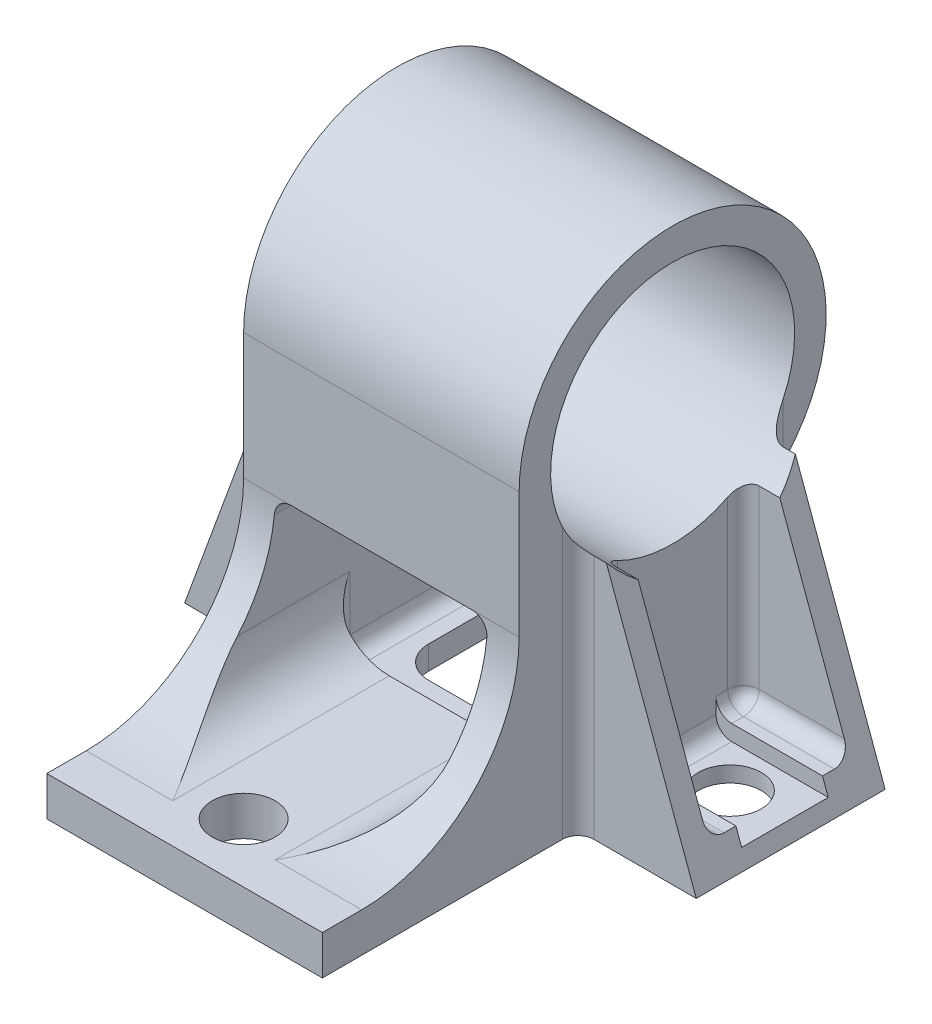
SolidWorks part; units mm, degrees
material "7075-T6 (SN)"
ref_plane "Płaszczyzna przednia" through (0, 0, 0) normal (0, 0, 1) x (1, 0, 0)
ref_plane "Płaszczyzna górna" through (0, 0, 0) normal (0, 1, 0) x (1, 0, 0)
ref_plane "Płaszczyzna prawa" through (0, 0, 0) normal (1, 0, 0) x (0, 0, -1)
sketch "Szkic1" plane through (0, 0, 0) normal (1, 0, 0) x (0, 0, -1)
  line L1 (-29.5, -41) -> (19.5, -41)
  line L2 (19.5, -41) -> (19.5, 0)
  line L4 (-44.5, -41) -> (-29.5, -41)
  line L5 (-44.5, -41) -> (-44.5, -36)
  line L6 (-44.5, -36) -> (-39.5, -36)
  line L8 (-19.5, 0) -> (-19.5, -16)
  circle A0 centre (0, 0) radius 15.5
  arc A1 (19.5, 0) -> (-19.5, 0) centre (0, 0) ccw
  arc A2 (-39.5, -36) -> (-19.5, -16) centre (-39.5, -16) ccw
  circle A3 centre (0, 0) radius 19.5 construction
  point P11 (19.5, 0)
  dimension "D1" = 31
  dimension "D5" = 20
  dimension "D3" = 41
  dimension "D4" = 25
  dimension "D6" = 5
  dimension "D2" = 4
extrude "Dodanie-wyciągnięcie2" add sketch "Szkic1" along normal mid plane 35
sketch "Szkic3" plane through (0, 0, -19.5) normal (0, 0, -1) x (-1, 0, 0)
  line L0 (-17.5, -41) -> (17.5, -41) construction
  line L1 (-13.5, -41) -> (13.5, -41)
  line L2 (-13.5, -41) -> (-13.5, -16)
  line L3 (-13.5, -16) -> (13.5, -16)
  line L4 (13.5, -41) -> (13.5, -16)
  line L5 (-17.5, -41) -> (-17.5, 0) construction
  line L6 (17.5, -41) -> (17.5, 0) construction
  line L7 (-17.5, 0) -> (17.5, 0) construction
  dimension "D1" = 4
  dimension "D2" = 4
  dimension "D3" = 16
extrude "Wytnij-wyciągnięcie2" cut sketch "Szkic3" against normal through all
sketch "Szkic5" plane through (0, -41, 0) normal (0, -1, 0) x (1, 0, 0)
  line L0 (-17.5, 44.5) -> (-17.5, -19.5) construction
  line L1 (17.5, -19.5) -> (-17.5, -19.5)
  line L2 (17.5, -19.5) -> (17.5, -4.5)
  line L3 (17.5, -4.5) -> (-17.5, -4.5)
  line L4 (-17.5, -19.5) -> (-17.5, -4.5)
  line L6 (17.5, 44.5) -> (-17.5, 44.5)
  line L7 (17.5, 44.5) -> (17.5, 29.5)
  line L8 (17.5, 29.5) -> (-17.5, 29.5)
  line L9 (-17.5, 44.5) -> (-17.5, 29.5)
  dimension "D1" = 15
  dimension "D2" = 15
extrude "Dodanie-wyciągnięcie4" add sketch "Szkic5" against normal blind 5
sketch "Szkic6" plane through (0, -36, 0) normal (0, 1, 0) x (1, 0, 0)
  line L0 (-13.5, -29.5) -> (13.5, -29.5) construction
  line L3 (-17.5, -39.5) -> (-17.5, -44.5) construction
  line L4 (13.5, 4.5) -> (-13.5, 4.5) construction
  line L5 (-17.5, -44.5) -> (-17.5, 19.5) construction
  circle A0 centre (0, -37) radius 4
  circle A1 centre (0, 12) radius 4
  dimension "D1" = 8
  dimension "D4" = 8
  dimension "D6" = 17.5
  dimension "D2" = 7.5
  dimension "D3" = 17.5
  dimension "D5" = 7.5
extrude "Wytnij-wyciągnięcie3" cut sketch "Szkic6" against normal through all
sketch "Szkic8" plane through (0, 0, 0) normal (0, 0, 1) x (1, 0, 0)
  line L0 (17.5, -41) -> (32.5, -41)
  line L1 (32.5, -41) -> (17.5, 0)
  line L2 (-17.5, -41) -> (-32.5, -41)
  line L3 (-32.5, -41) -> (-17.5, 0)
  line L4 (17.5, 0) -> (17.5, -41)
  line L5 (-17.5, 0) -> (-17.5, -41)
  dimension "D1" = 15
  dimension "D2" = 15
extrude "Dodanie-wyciągnięcie5" add sketch "Szkic8" against normal mid plane 24
sketch "Szkic9" plane through (0, 0, 0) normal (0, 1, 0) x (1, 0, 0)
  line L0 (-17.5, 12) -> (-17.5, -12) construction
  line L1 (-17.5, 9) -> (-32.5, 9)
  line L2 (-17.5, 9) -> (-17.5, -9)
  line L3 (-17.5, -9) -> (-32.5, -9)
  line L4 (-32.5, 9) -> (-32.5, -9)
  line L5 (-32.5, 12) -> (-32.5, -12) construction
  line L6 (-17.5, 12) -> (-32.5, 12) construction
  line L7 (-17.5, -12) -> (-32.5, -12) construction
  line L8 (17.5, -19.5) -> (17.5, 19.5) construction
  line L9 (17.5, 9) -> (32.5, 9)
  line L10 (17.5, 9) -> (17.5, -9)
  line L11 (17.5, -9) -> (32.5, -9)
  line L12 (32.5, 9) -> (32.5, -9)
  line L13 (32.5, 12) -> (32.5, -12) construction
  line L14 (32.5, 12) -> (17.5, 12) construction
  line L15 (32.5, -12) -> (17.5, -12) construction
  dimension "D1" = 3
  dimension "D2" = 3
  dimension "D3" = 3
  dimension "D4" = 3
extrude "Wytnij-wyciągnięcie4" cut sketch "Szkic9" along normal through all and the other way offset from surface 2 other way up to face at (0, -41, 41)
sketch "Szkic10" plane through (0, 0, 0) normal (1, 0, 0) x (0, 0, -1)
  circle A0 centre (0, 0) radius 15.5
extrude "Wytnij-wyciągnięcie5" cut sketch "Szkic10" against normal through all both and the other way through all
sketch "Szkic11" plane through (0, -39, 0) normal (0, 1, 0) x (1, 0, 0)
  line L0 (-31.7683, -9) -> (-31.7683, 9) construction
  line L1 (31.7683, 9) -> (31.7683, -9) construction
  circle A0 centre (-24.7683, 0) radius 4
  circle A1 centre (24.7683, 0) radius 4
  dimension "D1" = 8
  dimension "D3" = 8
  dimension "D2" = 7
  dimension "D4" = 7
extrude "Wytnij-wyciągnięcie6" cut sketch "Szkic11" against normal through all both and the other way through all
sketch "Szkic12" plane through (0, -41, 0) normal (0, -1, 0) x (1, 0, 0)
  line L0 (17.5, -19.5) -> (-17.5, -19.5) construction
  line L1 (-13.5, -4.5) -> (12.5, -4.5)
  line L2 (-13.5, -4.5) -> (-13.5, -19.5)
  line L3 (-13.5, -19.5) -> (12.5, -19.5)
  line L4 (12.5, -4.5) -> (12.5, -19.5)
extrude "Wytnij-wyciągnięcie7" cut sketch "Szkic12" against normal blind 5
sketch "Szkic13" plane through (0, -41, 0) normal (0, -1, 0) x (1, 0, 0)
  line L0 (-13.5, 29.5) -> (-13.5, -19.5) construction
  line L1 (-13.5, 12) -> (13.5, 12)
  line L2 (-13.5, 12) -> (-13.5, -12)
  line L3 (-13.5, -12) -> (13.5, -12)
  line L4 (13.5, 12) -> (13.5, -12)
  line L5 (13.5, 29.5) -> (13.5, -4.5) construction
extrude "Dodanie-wyciągnięcie6" add sketch "Szkic13" against normal blind 3
sketch "Szkic14" plane through (0, -41, 0) normal (0, -1, 0) x (1, 0, 0)
  line L0 (13.5, 25.2297) -> (13.5, -14.9592) construction
  line L1 (-5.5, 8) -> (5.5, 8)
  line L2 (-9.5, 4) -> (-9.5, -4)
  line L3 (-5.5, -8) -> (5.5, -8)
  line L4 (9.5, 4) -> (9.5, -4)
  line L5 (13.5, 29.5) -> (13.5, 12) construction
  line L6 (13.5, 29.5) -> (13.5, 12) construction
  line L7 (-13.5, 20.75) -> (-13.5, -14.9592) construction
  line L8 (-13.5, 29.5) -> (-13.5, 12) construction
  line L9 (-13.5, -12) -> (-13.5, -19.5) construction
  line L10 (13.5, 12) -> (-13.5, 12) construction
  line L11 (-13.5, -12) -> (12.5, -12) construction
  arc A0 (5.5, -8) -> (9.5, -4) centre (5.5, -4) ccw
  arc A1 (5.5, 8) -> (9.5, 4) centre (5.5, 4) cw
  arc A2 (-5.5, 8) -> (-9.5, 4) centre (-5.5, 4) ccw
  arc A3 (-9.5, -4) -> (-5.5, -8) centre (-5.5, -4) ccw
  dimension "D5" = 4
  dimension "D1" = 4
  dimension "D2" = 4
  dimension "D3" = 4
  dimension "D4" = 4
extrude "Wytnij-wyciągnięcie8" cut sketch "Szkic14" against normal blind 3
sketch "Szkic15" plane through (0, 0, 0) normal (1, 0, 0) x (0, 0, -1)
  line L0 (19.5, 0) -> (19.5, -41)
  line L1 (19.5, -41) -> (12, -41)
  line L2 (12, -41) -> (12, -15.3704)
  line L3 (12, -9.8107) -> (12, -41) construction
  arc A1 (12, -15.3704) -> (19.5, 0) centre (0, 0) ccw
  point P11 (19.5, 0)
extrude "Wytnij-wyciągnięcie9" cut sketch "Szkic15" against normal through all both and the other way through all contours A1 L0 L1 L2
fillet "Zaokrąglenie1" radius 10 1 edges at (0, -15.3704, -12)
fillet "Zaokrąglenie2" radius 2 4 edges at (-17.5, -25.4054, 12) (17.5, -25.4054, 12) (17.5, -14.732, -12) (-17.5, -14.732, -12)
fillet "Zaokrąglenie4" radius 2 4 edges at (13.5, -38.5, 29.5) (-13.5, -38.5, 29.5) (-13.5, -39.5, 12) (13.5, -39.5, 12)
fillet "Zaokrąglenie5" radius 2 7 edges at (17.5, -39, 0) (17.5, -25.8097, -9) (17.5, -25.8097, 9) (-17.5, -25.8097, -9) (-17.5, -39, 0) (-17.5, -25.8097, 9) (-13.5, -38, 1)
fillet "Zaokrąglenie6" radius 2 2 edges at (13.5, -16, 3.4044) (-13.5, -16, 3.4044)
sketch "Szkic16" plane through (0, 0, -12) normal (0, 0, -1) x (-1, 0, 0)
  line L1 (-13.5, -36) -> (-12.5, -36)
  line L2 (-13.5, -36) -> (-13.5, -38)
  line L3 (-13.5, -38) -> (-12.5, -38)
  line L4 (-12.5, -36) -> (-12.5, -38)
extrude "Wytnij-wyciągnięcie10" cut sketch "Szkic16" against normal blind 10
fillet "Zaokrąglenie8" radius 2 1 edges at (13.5, -38, 1)
sketch "Szkic17" plane through (0, -39, 0) normal (0, 1, 0) x (1, 0, 0)
  line L20 (17.5, -19.5) -> (17.5, 19.5) construction
  line L21 (31.7683, -9) -> (17.4462, -9)
  line L22 (31.7683, -9) -> (31.7683, -5.5)
  line L23 (31.7683, -5.5) -> (17.4462, -5.5)
  line L24 (17.4462, -9) -> (17.4462, -5.5)
  line L25 (31.7683, 9) -> (17.5, 9)
  line L26 (31.7683, 9) -> (31.7683, 5.5)
  line L27 (31.7683, 5.5) -> (17.5, 5.5)
  line L28 (17.5, 9) -> (17.5, 5.5)
  line L29 (-17.5, 19.5) -> (-17.5, -19.5) construction
  line L30 (-31.7683, 9) -> (-17.5, 9)
  line L31 (-31.7683, 9) -> (-31.7683, 5.5)
  line L32 (-31.7683, 5.5) -> (-17.5, 5.5)
  line L33 (-17.5, 9) -> (-17.5, 5.5)
  line L34 (-31.7683, -9) -> (-31.7683, 9) construction
  line L35 (-31.7683, -5.5) -> (-17.5, -5.5)
  line L36 (-31.7683, -5.5) -> (-31.7683, -9)
  line L37 (-31.7683, -9) -> (-17.5, -9)
  line L38 (-17.5, -5.5) -> (-17.5, -9)
  dimension "D1" = 3.5
  dimension "D2" = 3.5
  dimension "D3" = 3.5
  dimension "D4" = 3.5
extrude "Dodanie-wyciągnięcie7" add sketch "Szkic17" along normal blind 2
sketch "Szkic18" plane through (0, 0, -12) normal (0, 0, -1) x (-1, 0, 0)
  line L0 (-29.7406, -33.4575) -> (-32.5, -41)
  line L1 (-32.5, -41) -> (-21.0893, -9.8107) construction
  line L2 (-32.5, -41) -> (-37.8396, -39.0465)
  line L3 (-37.8396, -39.0465) -> (-29.7406, -33.4575)
  line L4 (32.5, -41) -> (30.0683, -34.3534)
  line L5 (21.0893, -9.8107) -> (32.5, -41) construction
  line L6 (30.0683, -34.3534) -> (39.1291, -34.3534)
  line L7 (39.1291, -34.3534) -> (32.5, -41)
extrude "Wytnij-wyciągnięcie11" cut sketch "Szkic18" against normal through all
fillet "Zaokrąglenie9" radius 2 12 edges at (25.2683, -37, 9) (18.0858, -37, 8.4142) (17.5, -37, 6.25) (17.5, -37, -6.25) (18.0858, -37, -8.4142) (-25.2683, -37, -9) (-18.0858, -37, -8.4142) (-17.5, -37, -6.25) (-17.5, -37, 6.25) (-18.0858, -37, 8.4142) (25.2683, -37, -9) (-25.2683, -37, 9)
sketch "Szkic19" plane through (0, -36, 0) normal (0, 1, 0) x (1, 0, 0)
  line L0 (-17.5, -19.5) -> (-17.5, -39.5) construction
  line L1 (-17.5, -12) -> (17.5, -12)
  line L2 (-17.5, -12) -> (-17.5, -39.5)
  line L3 (-17.5, -39.5) -> (17.5, -39.5)
  line L4 (17.5, -12) -> (17.5, -39.5)
  line L6 (11.5, -12) -> (-11.5, -12) construction
extrude "Dodanie-wyciągnięcie12" add sketch "Szkic19" against normal up to surface (5 mm away) up to face at (0, -41, 0)
fillet "Zaokrąglenie10" radius 7 2 edges at (-13.5, -36, 25.75) (13.5, -36, 25.75)
fillet "Zaokrąglenie11" radius 2 5 edges at (13.5, -32.5, 12) (12.9142, -37.4142, 12) (-13.5, -32.5, 12) (-12.9142, -37.4142, 12) (0, -38, 12)
sketch "Szkic20" plane through (0, -41, 0) normal (0, -1, 0) x (1, 0, 0)
  circle A0 centre (0, 37) radius 4
extrude "Wytnij-wyciągnięcie12" cut sketch "Szkic20" against normal through all both and the other way through all
